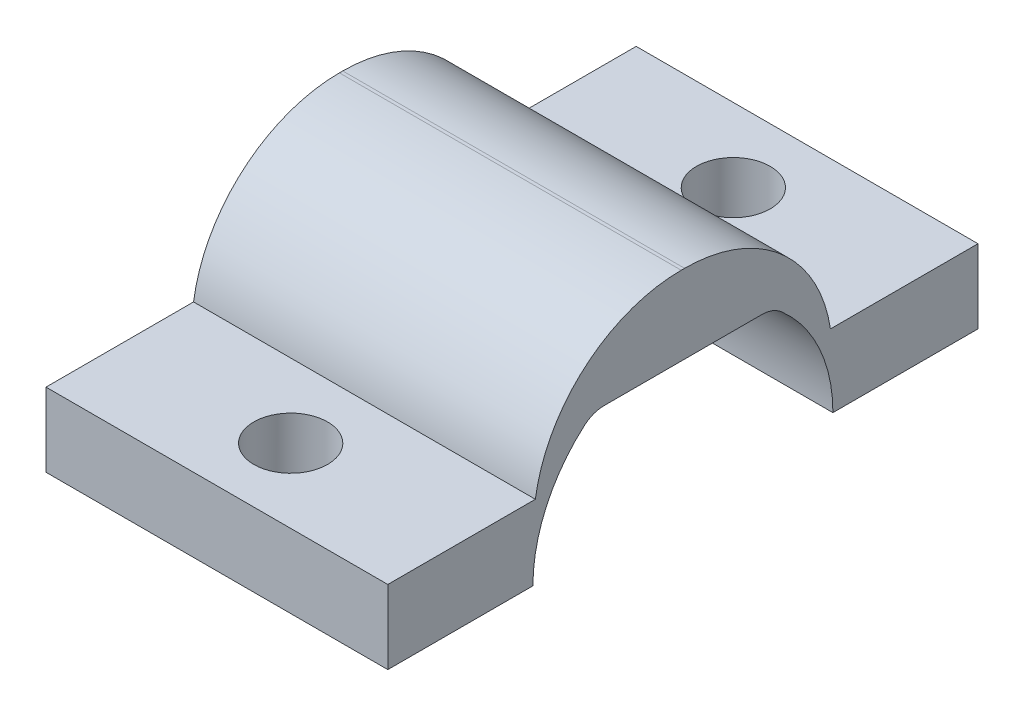
SolidWorks part; units mm, degrees
ref_plane "Plano frontal" through (0, 0, 0) normal (0, 0, 1) x (1, 0, 0)
ref_plane "Plano superior" through (0, 0, 0) normal (0, 1, 0) x (1, 0, 0)
ref_plane "Plano direito" through (0, 0, 0) normal (1, 0, 0) x (0, 0, -1)
sketch "Esboço1" plane through (0, 0, 0) normal (1, 0, 0) x (0, 0, -1)
  line L0 (0, -6.1) -> (0, -5.1)
  line L1 (0, 6.1) -> (0, 4.9)
  line L2 (-6.1, 0) -> (6.1, 0)
  line L3 (-3.6332, 4.9) -> (3.6332, 4.9)
  line L4 (-6.1, 0) -> (-10, 0)
  line L5 (6.1, 0) -> (10, 0)
  line L6 (-10, 0) -> (-10, 3)
  line L7 (10, 0) -> (10, 3)
  line L8 (-10, 3) -> (-6, 3)
  line L9 (-6, 3) -> (-6, 8.1)
  line L10 (-6, 8.1) -> (6, 8.1)
  line L11 (10, 3) -> (6, 3)
  line L12 (6, 3) -> (6, 8.1)
  circle A0 centre (0, 0) radius 6.1
  point P12 (0, 4.9)
  dimension "D1" = 12.2
  dimension "D2" = 1.2
  dimension "D3" = 1
  dimension "D4" = 3.9
  dimension "D5" = 3.9
  dimension "D6" = 3
  dimension "D7" = 3
  dimension "D8" = 2
extrude "Ressalto-extrusão1" add sketch "Esboço1" along normal blind 15.9 contours A0 L5 L7 L11 L12 L10 L9 L8 L6 L4 | L1 A0 L3 | L3 A0 L1 region at (0, 5.3843, -1.3823) region at (0, 5.9971, 1.9808) region at (0, 5.3843, 1.3823)
fillet "Filete1" radius 6 2 edges at (7.95, 8.1, 6) (7.95, 8.1, -6)
fillet "Filete2" radius 1.2 2 edges at (7.95, 4.9, -3.6332) (7.95, 4.9, 3.6332)
sketch "Esboço3" plane through (0, 3, 0) normal (0, 1, 0) x (1, 0, 0)
  line L0 (0, 10) -> (2, 10)
  line L1 (0, 10) -> (0, -10.0535)
  line L2 (2, 10) -> (2, -10.0535)
  line L3 (0, -10.0535) -> (2, -10.0535)
  line L4 (15.9, 10) -> (0, 10) construction
  dimension "D1" = 2
extrude "Corte-extrusão2" cut sketch "Esboço3" against normal through all both and the other way through all
sketch "Esboço4" plane through (0, 0, 10) normal (0, 0, 1) x (1, 0, 0)
  line L1 (2, 3) -> (15.9, 3)
  line L2 (2, 3) -> (2, 0)
  line L3 (2, 0) -> (15.9, 0)
  line L4 (15.9, 3) -> (15.9, 0)
extrude "Ressalto-extrusão2" add sketch "Esboço4" along normal blind 2
sketch "Esboço5" plane through (0, 0, -10) normal (0, 0, -1) x (-1, 0, 0)
  line L1 (-15.9, 3) -> (-2, 3)
  line L2 (-15.9, 3) -> (-15.9, 0)
  line L3 (-15.9, 0) -> (-2, 0)
  line L4 (-2, 3) -> (-2, 0)
extrude "Ressalto-extrusão3" add sketch "Esboço5" along normal blind 2
sketch "Esboço8" plane through (0, 3, 0) normal (0, 1, 0) x (1, 0, 0)
  line L0 (2, -9) -> (15.9, -9)
  line L1 (2, -12) -> (2, -6) construction
  line L2 (15.9, -12) -> (15.9, -6) construction
  line L3 (2, 9) -> (15.9, 9)
  line L4 (2, 12) -> (2, 6) construction
  line L5 (15.9, 12) -> (15.9, 6) construction
  circle A0 centre (8.95, 9) radius 1.5
  circle A1 centre (8.95, -9) radius 1.5
  dimension "D1" = 3
  dimension "D2" = 3
extrude "Corte-extrusão3" cut sketch "Esboço8" against normal blind 10 contours L3 A0 | L3 A0 | L0 A1 | L0 A1 region at (8.95, 3, 8.3634) region at (8.95, 3, 9.6366) region at (8.95, 3, -9.6366) region at (8.95, 3, -8.3634)
